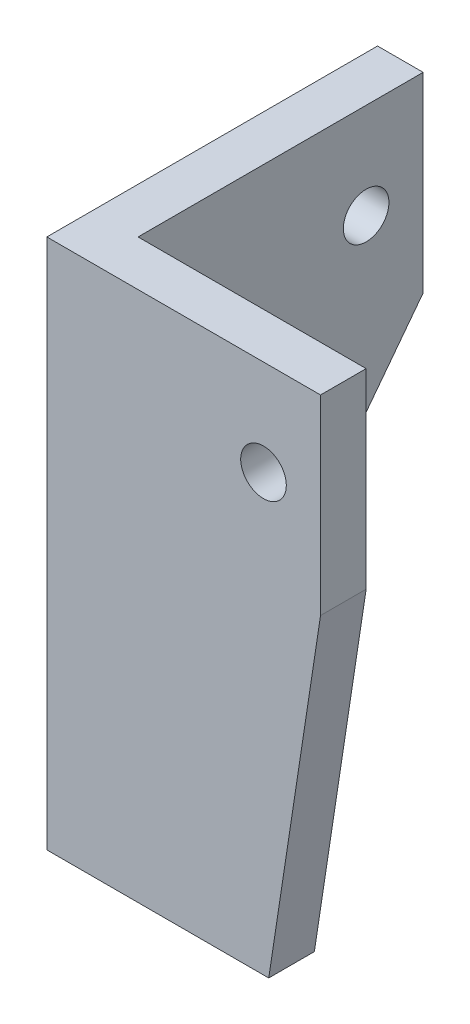
SolidWorks part; units mm, degrees
ref_plane "Front Plane" through (0, 0, 0) normal (0, 0, 1) x (1, 0, 0)
ref_plane "Top Plane" through (0, 0, 0) normal (0, 1, 0) x (1, 0, 0)
ref_plane "Right Plane" through (0, 0, 0) normal (1, 0, 0) x (0, 0, -1)
sketch "Sketch1" plane through (0, 0, 0) normal (0, 0, 1) x (1, 0, 0)
  line L0 (-92, -50.55) -> (-75, -50.55) construction
  line L4 (-90, -50.55) -> (-75, -50.55)
  line L7 (-80, -1) -> (-70, -1)
  line L9 (-80, -1) -> (-90, -1) construction
  line L12 (-80, -1) -> (-90, -1)
  line L14 (80, -1) -> (-80, -1) construction
  line L15 (-70, -1) -> (-70, -17.75)
  line L16 (-80, -17.75) -> (-21.5, -17.75) construction
  line L19 (-75, -50.55) -> (-70, -17.75)
  line L21 (-90, -17.75) -> (-90, -1) construction
  line L22 (-90, -17.75) -> (-90, -1)
  line L23 (-90, -17.75) -> (-90, -50.55)
extrude "Boss-Extrude1" add sketch "Sketch1" along normal blind 4
sketch "Sketch2" plane through (-90, 0, 0) normal (-1, 0, 0) x (0, 0, 1)
  line L2 (0, -1) -> (-25, -1)
  line L4 (0, -1) -> (0, -50.55)
  line L5 (0, -50.55) -> (4, -50.55)
  line L6 (4, -50.55) -> (4, -1)
  line L7 (4, -1) -> (0, -1)
  line L9 (0, -50.55) -> (4, -50.55)
  line L10 (4, -50.55) -> (4, -1)
  line L11 (4, -1) -> (0, -1)
  line L12 (-10, -1) -> (-222, -1) construction
  line L14 (-25, -1) -> (-25, -17.75)
  line L15 (-222, -17.75) -> (-10, -17.75) construction
  line L16 (-25, -17.75) -> (0, -50.55)
  dimension "D1" = 0
extrude "Boss-Extrude2" add sketch "Sketch2" along normal blind 4
sketch "Sketch3" plane through (0, 0, 4) normal (0, 0, 1) x (1, 0, 0)
  line L0 (-94, -50.55) -> (-94, -49.55)
  line L1 (-94, -49.55) -> (-94, -47.55)
  line L2 (-94, -47.55) -> (-74.5427, -47.55)
  line L5 (-75, -50.55) -> (-70, -17.75)
  line L6 (-70, -17.75) -> (-70, -1)
  line L7 (-70, -1) -> (-94, -1)
  line L8 (-94, -1) -> (-94, -50.55)
  line L9 (-94, -50.55) -> (-75, -50.55)
  line L10 (-75, -50.55) -> (-74.5427, -47.55)
  line L13 (-94, -47.55) -> (-94, -50.55)
  line L14 (-94, -50.55) -> (-75, -50.55)
  line M6 (-75, -50.55) -> (-70, -17.75)
  line M9 (-94, -1) -> (-94, -50.55)
  line M10 (-94, -50.55) -> (-75, -50.55)
  dimension "D1" = 0
extrude "Cut-Extrude1" cut sketch "Sketch3" against normal through all contours L2 M9 M10 M6 region at (-84.3852, -49.0441, 4)
sketch "Sketch4" plane through (0, 0, 4) normal (0, 0, 1) x (1, 0, 0)
  circle A0 centre (-75, -9.375) radius 2
extrude "Cut-Extrude2" cut sketch "Sketch4" against normal up to surface (4 mm away) up to face at (-78.9085, -22.97, 0)
sketch "Sketch5" plane through (-94, 0, 0) normal (-1, 0, 0) x (0, 0, 1)
  line L0 (-25, -9.375) -> (-20, -9.375)
  line L1 (-25, -1) -> (-25, -17.75) construction
  circle A0 centre (-20, -9.375) radius 2
extrude "Cut-Extrude3" cut sketch "Sketch5" against normal up to surface (4 mm away) contours A0 region at (-94, -11.3184, -20) up to face at (-90, -22.97, -10.4573)
